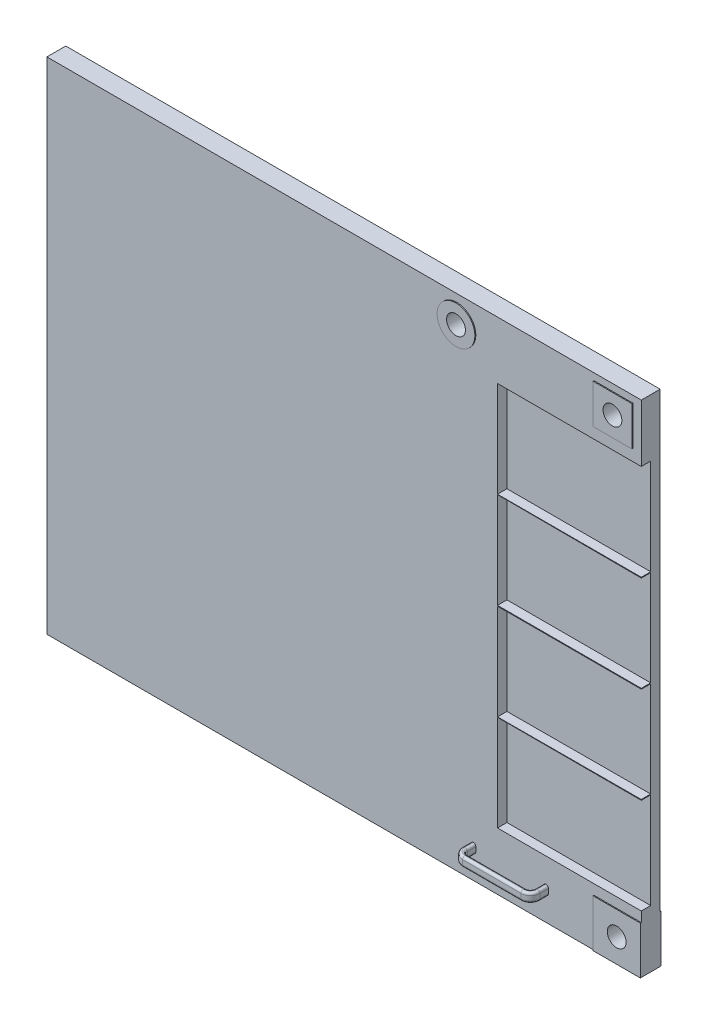
SolidWorks part; units mm, degrees
ref_plane "Front Plane" through (0, 0, 0) normal (0, 0, 1) x (1, 0, 0)
ref_plane "Top Plane" through (0, 0, 0) normal (0, 1, 0) x (1, 0, 0)
ref_plane "Right Plane" through (0, 0, 0) normal (1, 0, 0) x (0, 0, -1)
sketch "Sketch1" plane through (0, 0, 0) normal (0, 0, 1) x (1, 0, 0)
  line L1 (0, 0) -> (63, 0)
  line L2 (0, 0) -> (0, 53)
  line L3 (0, 53) -> (63, 53)
  line L4 (63, 0) -> (63, 53)
extrude "Boss-Extrude1" add sketch "Sketch1" against normal blind 2
sketch "Sketch2" plane through (0, 0, 0) normal (0, 0, 1) x (1, 0, 0)
  line L1 (63, 26.54) -> (47.76, 26.54)
  line L2 (63, 26.54) -> (63, 36.66)
  line L3 (63, 46.9) -> (47.76, 46.9)
  line L4 (47.76, 26.54) -> (47.76, 36.7)
  line L5 (63, 26.54) -> (63, 36.66) construction
  line L6 (47.76, 36.7) -> (63, 36.66)
  line L7 (63, 46.9) -> (63, 36.74) construction
  line L8 (63, 36.74) -> (47.76, 36.74)
  line L9 (47.76, 36.74) -> (47.76, 46.9)
  line L10 (63, 36.74) -> (63, 46.9)
  line L11 (63, 26.5) -> (53.226, 26.5) construction
  line L12 (63, 0) -> (63, 53) construction
  line L13 (63, 6.1) -> (63, 16.26) construction
  line L14 (63, 26.46) -> (63, 16.34) construction
  line L15 (63, 16.26) -> (63, 6.1)
  line L16 (47.76, 16.26) -> (47.76, 6.1)
  line L17 (63, 16.26) -> (47.76, 16.26)
  line L18 (47.76, 16.3) -> (63, 16.34)
  line L19 (47.76, 26.46) -> (47.76, 16.3)
  line L20 (63, 6.1) -> (47.76, 6.1)
  line L21 (63, 26.46) -> (63, 16.34)
  line L22 (63, 26.46) -> (47.76, 26.46)
extrude "Cut-Extrude1" cut sketch "Sketch2" against normal blind 1
sketch "Sketch4" plane through (0, 0, 0) normal (0, 0, 1) x (1, 0, 0)
  line L0 (63, 0) -> (63, 6.1) construction
  line L1 (63, 5.0377) -> (57.9864, 5.0377)
  line L2 (63, 5.0377) -> (63, 0)
  line L3 (63, 0) -> (57.9864, 0)
  line L4 (57.9864, 5.0377) -> (57.9864, 0)
  line L5 (0, 0) -> (63, 0) construction
  line L7 (62.0965, 52.2749) -> (57.9864, 52.2749)
  line L8 (62.0965, 52.2749) -> (62.0965, 48.1145)
  line L9 (62.0965, 48.1145) -> (57.9864, 48.1145)
  line L10 (57.9864, 52.2749) -> (57.9864, 48.1145)
  circle A0 centre (60.4932, 2.5188) radius 1
  circle A1 centre (60.0414, 50.1947) radius 1
  circle A2 centre (43.4606, 50.1947) radius 2
  circle A3 centre (43.4606, 50.1947) radius 1
extrude "Boss-Extrude2" add sketch "Sketch4" against normal blind 2.1 and the other way blind 0.1
sketch "Sketch5" plane through (0, 0, 0) normal (0, 0, 1) x (1, 0, 0)
  circle A0 centre (60.4932, 2.5188) radius 1
  circle A1 centre (60.0414, 50.1947) radius 1
  circle A2 centre (43.4606, 50.1947) radius 1
extrude "Cut-Extrude2" cut sketch "Sketch5" against normal blind 2
ref_plane "Plane1" through (0, 3, 0) normal (0, -1, 0) x (-1, 0, 0)
sketch "Sketch6" plane through (0, 3, 0) normal (0, -1, 0) x (-1, 0, 0)
  line L0 (-45.2088, 0.6706) -> (-45.2088, -1.6503)
  line L1 (-45.2088, -1.6503) -> (-52.9034, -1.6503)
  line L2 (-52.9034, -1.6503) -> (-52.9034, 0.6706)
extrude "Extrude-Thin1" add sketch "Sketch6" along normal blind 0.5 and the other way blind 0.5 thin contours L0 L1 L2 thin type mid plane wall 0.5
fillet "Fillet1" radius 0.25 20 edges at (45.4588, 3.5, 0.4502) (45.6052, 3.5, 1.2539) (52.6534, 3.5, 0.4502) (52.507, 3.5, 1.2539) (45.4588, 2.5, 0.4502) (45.6052, 2.5, 1.2539) (52.6534, 2.5, 0.4502) (52.507, 2.5, 1.2539) (44.9588, 3.5, 0.4502) (45.2517, 3.5, 1.6074) (53.1534, 3.5, 0.4502) (52.8605, 3.5, 1.6074) (44.9588, 2.5, 0.4502) (53.1534, 2.5, 0.4502) (52.8605, 2.5, 1.6074) (49.0561, 2.5, 1.9003) (49.0561, 3.5, 1.4003) (49.0561, 2.5, 1.4003) (49.0561, 3.5, 1.9003) (45.2517, 2.5, 1.6074)
